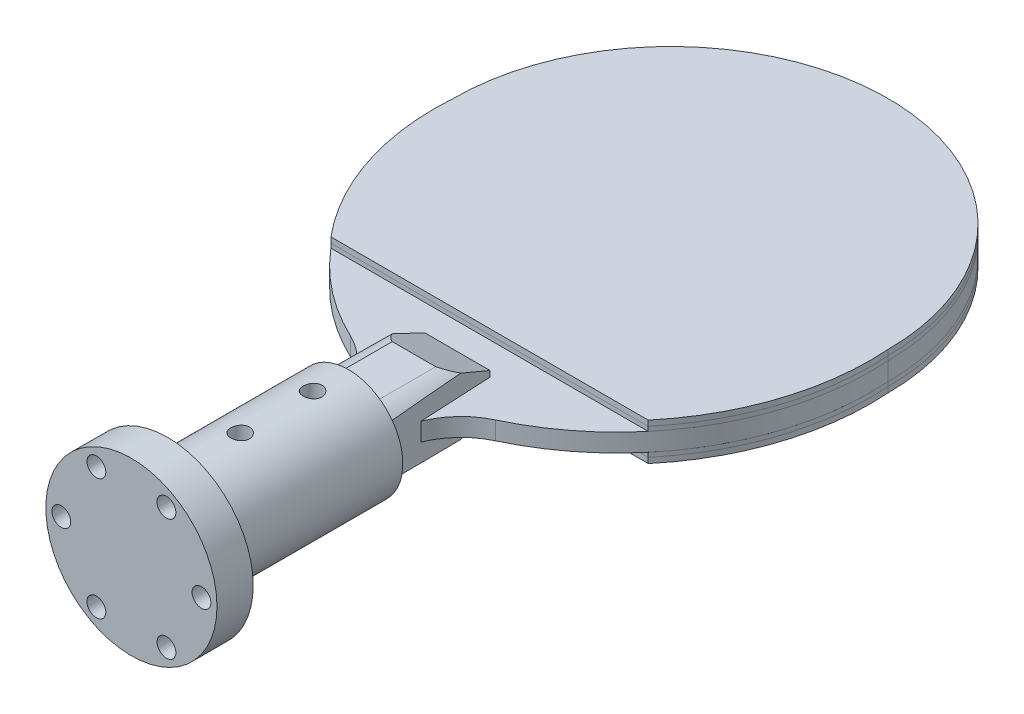
SolidWorks part; units mm, degrees
material "Beech"
ref_plane "Front Plane" through (0, 0, 0) normal (0, 0, 1) x (1, 0, 0)
ref_plane "Top Plane" through (0, 0, 0) normal (0, 1, 0) x (1, 0, 0)
ref_plane "Right Plane" through (0, 0, 0) normal (1, 0, 0) x (0, 0, -1)
sketch "Sketch2" plane through (0, 0, 0) normal (0, 1, 0) x (1, 0, 0)
  line L0 (0, -1000) -> (0, 49000) construction
  line L1 (-12.7, -100.1709) -> (-16.3767, -173.7041)
  line L2 (-13.8398, -176.3709) -> (13.8398, -176.3709)
  line L3 (12.7, -100.1709) -> (16.3767, -173.7041)
  arc A0 (-76.2, 0) -> (76.2, 0) centre (0, 0) cw
  arc A1 (76.2, 0) -> (25.4, -86.7792) centre (-12.4729, -6.35) cw
  arc A2 (-76.2, 0) -> (-25.4, -86.7792) centre (12.4729, -6.35) ccw
  arc A3 (25.4, -86.7792) -> (12.7, -100.1709) centre (36.2208, -109.7589) ccw
  arc A4 (-25.4, -86.7792) -> (-12.7, -100.1709) centre (-36.2208, -109.7589) cw
  arc A5 (-16.3767, -173.7041) -> (-13.8398, -176.3709) centre (-13.8398, -173.8309) ccw
  arc A6 (16.3767, -173.7041) -> (13.8398, -176.3709) centre (13.8398, -173.8309) cw
  point P17 (0, -176.3709)
  point P19 (-16.51, -176.3709)
  point P22 (16.51, -176.3709)
  dimension "D1" = 76.2
  dimension "D3" = 88.9
  dimension "D6" = 25.4
  dimension "D9" = 2.54
  dimension "D2" = 50.8
  dimension "D4" = 6.35
  dimension "D5" = 25.4
  dimension "D7" = 76.2
  dimension "D8" = 16.51
extrude "Boss-Extrude1" add sketch "Sketch2" along normal blind 6.35
sketch "Sketch3" plane through (0, 6.35, 0) normal (0, 1, 0) x (1, 0, 0)
  line L0 (-55.6232, -63.5) -> (55.6232, -63.5)
  arc A0 (76.2, 0) -> (-76.2, 0) centre (0, 0) ccw construction
  arc A1 (-76.2, 0) -> (-25.4, -86.7792) centre (12.4729, -6.35) ccw construction
  arc A2 (25.4, -86.7792) -> (76.2, 0) centre (-12.4729, -6.35) ccw construction
  arc A3 (76.2, 0) -> (-76.2, 0) centre (0, 0) ccw
  arc A4 (-76.2, 0) -> (-55.6232, -63.5) centre (12.4729, -6.35) ccw
  arc A5 (55.6232, -63.5) -> (76.2, 0) centre (-12.4729, -6.35) ccw
  dimension "D1" = 63.5
extrude "Boss-Extrude2" add sketch "Sketch3" along normal blind 1.524 separate body
sketch "Sketch4" plane through (0, 7.874, 0) normal (0, 1, 0) x (1, 0, 0)
  line L0 (-55.6232, -63.5) -> (55.6232, -63.5) construction
  line L1 (-55.6232, -63.5) -> (55.6232, -63.5)
  arc A0 (-76.2, 0) -> (-55.6232, -63.5) centre (12.4729, -6.35) ccw construction
  arc A1 (76.2, 0) -> (-76.2, 0) centre (0, 0) ccw construction
  arc A2 (55.6232, -63.5) -> (76.2, 0) centre (-12.4729, -6.35) ccw construction
  arc A3 (-76.2, 0) -> (-55.6232, -63.5) centre (12.4729, -6.35) ccw
  arc A4 (76.2, 0) -> (-76.2, 0) centre (0, 0) ccw
  arc A5 (55.6232, -63.5) -> (76.2, 0) centre (-12.4729, -6.35) ccw
extrude "Boss-Extrude4" add sketch "Sketch4" along normal blind 1.905 separate body
ref_plane "Plane1" through (0, 3.175, 0) normal (0, 1, 0) x (1, 0, 0)
sketch "Sketch5" plane through (0, 0, 0) normal (0, -1, 0) x (1, 0, 0)
  line L0 (55.6232, 63.5) -> (-55.6232, 63.5)
  line L3 (12.7, 100.1709) -> (16.3767, 173.7041)
  line L4 (13.8398, 176.3709) -> (-13.8398, 176.3709)
  line L5 (-16.3767, 173.7041) -> (-12.7, 100.1709)
  arc A7 (-25.4, 86.7792) -> (-76.2, 0) centre (12.4729, 6.35) ccw
  arc A8 (-76.2, 0) -> (76.2, 0) centre (0, 0) ccw
  arc A9 (76.2, 0) -> (25.4, 86.7792) centre (-12.4729, 6.35) ccw
  arc A10 (12.7, 100.1709) -> (25.4, 86.7792) centre (36.2208, 109.7589) ccw
  arc A11 (16.3767, 173.7041) -> (13.8398, 176.3709) centre (13.8398, 173.8309) ccw
  arc A12 (-13.8398, 176.3709) -> (-16.3767, 173.7041) centre (-13.8398, 173.8309) ccw
  arc A13 (-25.4, 86.7792) -> (-12.7, 100.1709) centre (-36.2208, 109.7589) ccw
  arc A14 (-55.6232, 63.5) -> (-76.2, 0) centre (12.4729, 6.35) ccw
  arc A15 (-76.2, 0) -> (76.2, 0) centre (0, 0) ccw
  arc A16 (76.2, 0) -> (55.6232, 63.5) centre (-12.4729, 6.35) ccw
  dimension "D2" = 63.5
  dimension "D1" = 0
extrude "Boss-Extrude5" add sketch "Sketch5" along normal blind 1.524 separate body
sketch "Sketch6" plane through (0, -1.524, 0) normal (0, -1, 0) x (1, 0, 0)
  line L1 (55.6232, 63.5) -> (-55.6232, 63.5)
  line L2 (55.6232, 63.5) -> (-55.6232, 63.5)
  arc A3 (76.2, 0) -> (55.6232, 63.5) centre (-12.4729, 6.35) ccw
  arc A4 (-55.6232, 63.5) -> (-76.2, 0) centre (12.4729, 6.35) ccw
  arc A5 (-76.2, 0) -> (76.2, 0) centre (0, 0) ccw
  arc A6 (76.2, 0) -> (55.6232, 63.5) centre (-12.4729, 6.35) ccw
  arc A7 (-55.6232, 63.5) -> (-76.2, 0) centre (12.4729, 6.35) ccw
  arc A8 (-76.2, 0) -> (76.2, 0) centre (0, 0) ccw
  dimension "D1" = 0
extrude "Boss-Extrude6" add sketch "Sketch6" along normal blind 1.905 separate body
sketch "Sketch7" plane through (0, 6.35, 0) normal (0, 1, 0) x (1, 0, 0)
  line L0 (-12.7, -100.1709) -> (-16.3767, -173.7041) construction
  line L1 (16.3767, -173.7041) -> (12.7, -100.1709) construction
  line L2 (-13.8398, -176.3709) -> (13.8398, -176.3709) construction
  line L3 (-11.43, -74.7709) -> (-16.3767, -173.7041)
  line L4 (16.3767, -173.7041) -> (11.43, -74.7709)
  line L5 (-13.8398, -176.3709) -> (13.8398, -176.3709)
  line L6 (-11.43, -74.7709) -> (11.43, -74.7709)
  arc A0 (13.8398, -176.3709) -> (16.3767, -173.7041) centre (13.8398, -173.8309) ccw construction
  arc A1 (-16.3767, -173.7041) -> (-13.8398, -176.3709) centre (-13.8398, -173.8309) ccw construction
  arc A2 (13.8398, -176.3709) -> (16.3767, -173.7041) centre (13.8398, -173.8309) ccw
  arc A3 (-16.3767, -173.7041) -> (-13.8398, -176.3709) centre (-13.8398, -173.8309) ccw
  dimension "D1" = 101.6
extrude "Boss-Extrude7" add sketch "Sketch7" along normal blind 8.89
sketch "Sketch8" plane through (0, 0, 176.3709) normal (0, 0, 1) x (1, 0, 0)
  line L0 (-16.3798, 15.24) -> (-16.3798, 0) construction
  line L1 (-13.8398, 15.24) -> (13.8398, 15.24) construction
  line L2 (16.3798, 0) -> (16.3798, 15.24) construction
  line L4 (0, -1000) -> (0, 15.24) construction
  line L5 (16.3798, 15.24) -> (13.8398, 15.24) construction
  line L6 (-13.8398, 15.24) -> (-16.3798, 15.24) construction
  line L7 (-13.8398, 15.24) -> (-7.62, 15.24)
  line L8 (16.3798, 15.24) -> (13.8398, 15.24)
  line L9 (16.3798, 7.62) -> (16.3798, 15.24)
  line L10 (-13.8398, 15.24) -> (-16.3798, 15.24)
  line L11 (-16.3798, 15.24) -> (-16.3798, 7.62)
  line L12 (7.62, 15.24) -> (13.8398, 15.24)
  arc A0 (-16.3798, 7.62) -> (-7.62, 15.24) centre (-4.5865, 2.9076) cw
  arc A1 (16.3798, 7.62) -> (7.62, 15.24) centre (4.5865, 2.9076) ccw
  dimension "D2" = 12.7
  dimension "D3" = 12.7
  dimension "D1" = 15.24
extrude "Cut-Extrude1" cut sketch "Sketch8" against normal blind 101.6
sketch "Sketch9" plane through (0, 0, -0.1919) normal (1, 0, 0) x (0, 0, -1)
  line L0 (-74.9628, 8.382) -> (-90.2028, 15.24)
  line L1 (-74.9628, 13.606) -> (-74.9628, 6.35) construction
  line L2 (-74.9628, 15.24) -> (-176.5628, 15.24) construction
  line L3 (-90.2028, 15.24) -> (-74.9628, 15.24)
  line L4 (-74.9628, 15.24) -> (-74.9628, 8.382)
  dimension "D1" = 15.24
  dimension "D2" = 15.24
  dimension "D3" = 6.858
extrude "Cut-Extrude2" cut sketch "Sketch9" against normal mid plane 50.8
mirror "Mirror8" about plane through (0, 3.175, 0) normal (0, 1, 0) of "Cut-Extrude2", "Cut-Extrude1", "Boss-Extrude7"
sketch "Sketch10" plane through (0, 0, 176.3709) normal (0, 0, 1) x (1, 0, 0)
  line L0 (0, 15.24) -> (0, -8.89) construction
  line L1 (-7.62, 15.24) -> (7.62, 15.24) construction
  line L2 (-7.62, -8.89) -> (7.62, -8.89) construction
  line L3 (-16.3798, 3.175) -> (16.3798, 3.175) construction
  line L4 (-16.3798, 7.6201) -> (-16.3798, -1.2701) construction
  line L5 (16.3798, -1.27) -> (16.3798, 7.62) construction
  circle A1 centre (0, 3.175) radius 30
  dimension "D1" = 60
extrude "Boss-Extrude8" add sketch "Sketch10" along normal blind 12.7 and the other way blind 63.5
sketch "Sketch11" plane through (0, 0, 0) normal (0, 1, 0) x (1, 0, 0)
  line L0 (30, -112.8709) -> (-30, -112.8709) construction
  circle A0 centre (0, -125.5709) radius 3.302
  circle A1 centre (0, -150.9709) radius 3.302
  dimension "D1" = 6.604
  dimension "D2" = 25.4
  dimension "D3" = 12.7
extrude "Cut-Extrude3" cut sketch "Sketch11" against normal through all both and the other way through all
sketch "Sketch12" plane through (0, 0, 112.8709) normal (0, 0, -1) x (-1, 0, 0)
  circle A0 centre (0.0907, 2.8996) radius 24.7101 construction
  circle A1 centre (0.0907, 2.8996) radius 37.4101
  circle A2 centre (0.0907, 2.8996) radius 19.05
  dimension "D2" = 38.1
  dimension "D1" = 12.7
extrude "Cut-Extrude4" cut sketch "Sketch12" against normal blind 63.5
sketch "Sketch13" plane through (0, 0, 176.3709) normal (0, 0, -1) x (-1, 0, 0)
  line L0 (0, 33.175) -> (0, -26.825) construction
  line L1 (-30, 3.175) -> (-18.9573, 3.175) construction
  line L2 (19.1388, 3.175) -> (30, 3.175) construction
  circle A0 centre (0, 3.175) radius 30 construction
  circle A1 centre (0, 3.175) radius 30 construction
  circle A2 centre (0.0907, 2.8996) radius 19.05 construction
  circle A3 centre (0.0907, 2.8996) radius 19.05 construction
  circle A4 centre (24.5694, 3.175) radius 3.302
  dimension "D1" = 6.604
extrude "Cut-Extrude6" cut sketch "Sketch13" against normal through all
ref_axis "Axis1" through (0, 3.175, 176.3709) along (0, 0, 1)
pattern_circular "CirPattern1" count 6 over 360 about axis through (0, 3.175, 176.3709) along (0, 0, 1) of "Cut-Extrude6"
ref_point "OriginPoint"
